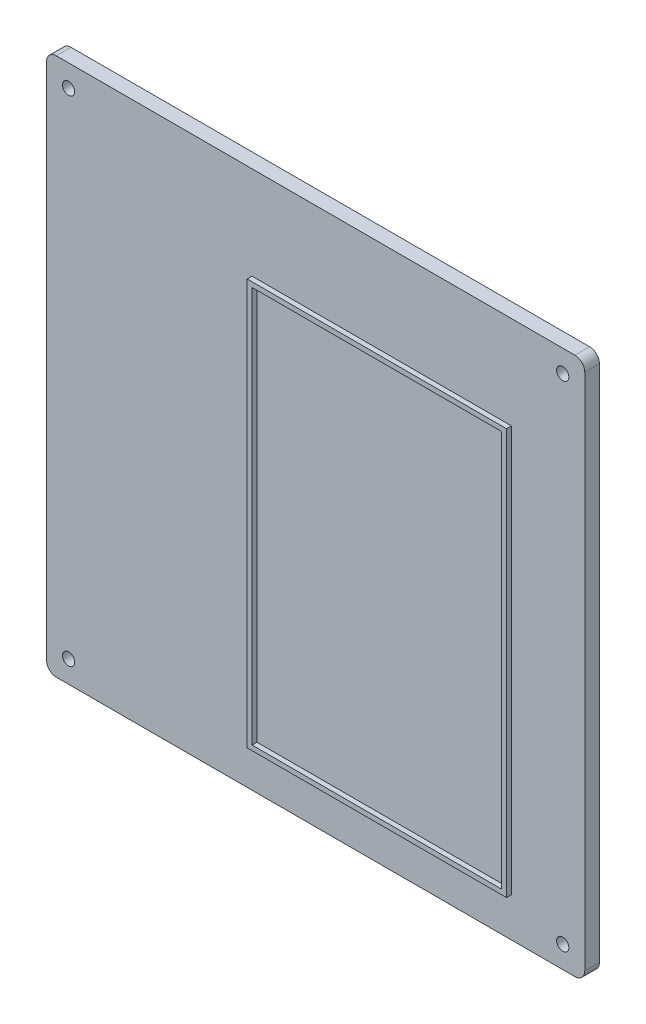
SolidWorks part; units mm, degrees
ref_plane "Plan de face" through (0, 0, 0) normal (0, 0, 1) x (1, 0, 0)
ref_plane "Plan de dessus" through (0, 0, 0) normal (0, 1, 0) x (1, 0, 0)
ref_plane "Plan de droite" through (0, 0, 0) normal (1, 0, 0) x (0, 0, -1)
sketch "Esquisse1" plane through (0, 0, 0) normal (0, 0, 1) x (1, 0, 0)
  line L1 (-138.1506, 106.4684) -> (81.8494, 106.4684)
  line L2 (-138.1506, 106.4684) -> (-138.1506, -113.5316)
  line L3 (-138.1506, -113.5316) -> (81.8494, -113.5316)
  line L4 (81.8494, 106.4684) -> (81.8494, -113.5316)
  line L5 (-129.1506, 97.4684) -> (72.8494, 97.4684) construction
  line L6 (-129.1506, 97.4684) -> (-129.1506, -104.5316) construction
  line L7 (-129.1506, -104.5316) -> (72.8494, -104.5316) construction
  line L8 (72.8494, 97.4684) -> (72.8494, -104.5316) construction
  line L9 (-129.1506, 97.4684) -> (72.8494, -104.5316) construction
  line L10 (-129.1506, -104.5316) -> (72.8494, 97.4684) construction
  circle A0 centre (-129.1506, 97.4684) radius 2.5
  circle A1 centre (72.8494, 97.4684) radius 2.5
  circle A2 centre (72.8494, -104.5316) radius 2.5
  circle A3 centre (-129.1506, -104.5316) radius 2.5
  point P8 (-28.1506, -3.5316)
  point P19 (-28.1506, -3.5316)
  dimension "D7" = 5
  dimension "D1" = 220
  dimension "D2" = 220
  dimension "D3" = 202
  dimension "D4" = 202
  dimension "D5" = 9
  dimension "D6" = 9
  dimension "D8" = 4
extrude "Boss.-Extru.1" add sketch "Esquisse1" along normal blind 6
fillet "Congé1" radius 4 4 edges at (-138.1506, -113.5316, 3) (81.8494, -113.5316, 3) (-138.1506, 106.4684, 3) (81.8494, 106.4684, 3)
sketch "Esquisse2" plane through (0, 0, 6) normal (0, 0, 1) x (1, 0, 0)
  line L0 (81.8494, -109.5316) -> (81.8494, 102.4684) construction
  line L1 (-52.1506, 66.4684) -> (49.8494, 66.4684)
  line L2 (-52.1506, 66.4684) -> (-52.1506, -95.5316)
  line L3 (-52.1506, -95.5316) -> (49.8494, -95.5316)
  line L4 (49.8494, 66.4684) -> (49.8494, -95.5316)
  line L5 (-52.1506, 66.4684) -> (49.8494, -95.5316) construction
  line L6 (-52.1506, -95.5316) -> (49.8494, 66.4684) construction
  line L7 (-54.1506, 68.4684) -> (51.8494, 68.4684)
  line L8 (-54.1506, 68.4684) -> (-54.1506, -97.5316)
  line L9 (-54.1506, -97.5316) -> (51.8494, -97.5316)
  line L10 (51.8494, 68.4684) -> (51.8494, -97.5316)
  line L11 (-54.1506, 68.4684) -> (51.8494, -97.5316) construction
  line L12 (-54.1506, -97.5316) -> (51.8494, 68.4684) construction
  line L13 (77.8494, 106.4684) -> (-134.1506, 106.4684) construction
  point P4 (-1.1506, -14.5316)
  point P9 (-1.1506, -14.5316)
  dimension "D1" = 106
  dimension "D2" = 166
  dimension "D3" = 102
  dimension "D4" = 162
  dimension "D5" = 2
  dimension "D6" = 2
  dimension "D7" = 30
  dimension "D8" = 38
extrude "Boss.-Extru.2" add sketch "Esquisse2" along normal blind 2 contours L8 L7 L10 L9 | L2 L1 L4 L3
